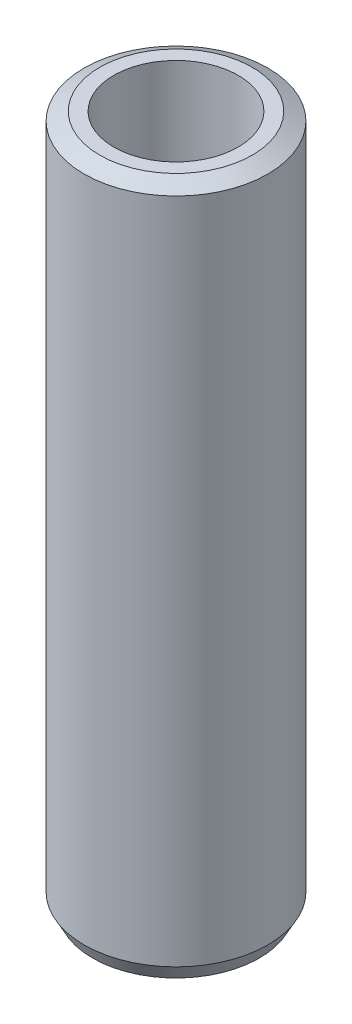
SolidWorks part; units mm, degrees
ref_plane "Front Plane" through (0, 0, 0) normal (0, 0, 1) x (1, 0, 0)
ref_plane "Top Plane" through (0, 0, 0) normal (0, 1, 0) x (1, 0, 0)
ref_plane "Right Plane" through (0, 0, 0) normal (1, 0, 0) x (0, 0, -1)
sketch "Sketch1" plane through (0, 0, 0) normal (0, 1, 0) x (1, 0, 0)
  circle A0 centre (0, 0) radius 57.5
  dimension "SHAFT_OD" = 115
extrude "Boss-Extrude1" add sketch "Sketch1" along normal blind 432.9224
sketch "Sketch2" plane through (0, 0, 0) normal (0, 1, 0) x (1, 0, 0)
  circle A0 centre (0, 0) radius 38.926
  dimension "BORE_D" = 77.852
extrude "Cut-Extrude1" cut sketch "Sketch2" along normal through all
chamfer "Chamfer1" distance 5.3173 angle 61.523 2 edges at (0, 432.9224, 57.5) (0, 0, 57.5) first distance on face at (0, 432.9224, 57.5) first distance on face at (0, 0, 38.926)
